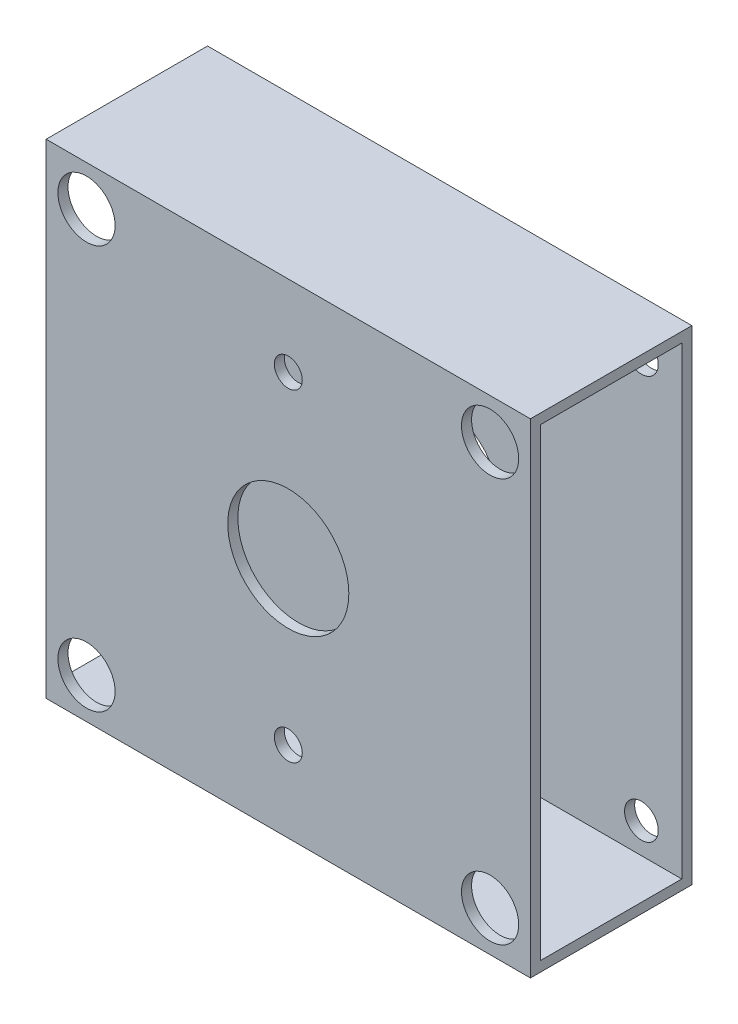
SolidWorks part; units mm, degrees
material "ALUMINUM 6061-T6"
ref_plane "Front Plane" through (0, 0, 0) normal (0, 0, 1) x (1, 0, 0)
ref_plane "Top Plane" through (0, 0, 0) normal (0, 1, 0) x (1, 0, 0)
ref_plane "Right Plane" through (0, 0, 0) normal (1, 0, 0) x (0, 0, -1)
sketch "Sketch1" plane through (0, 0, 0) normal (0, 0, 1) x (1, 0, 0)
  line L1 (-38.1, -38.1) -> (38.1, -38.1)
  line L2 (-38.1, -38.1) -> (-38.1, 38.1)
  line L3 (-38.1, 38.1) -> (38.1, 38.1)
  line L4 (38.1, -38.1) -> (38.1, 38.1)
  line L5 (-38.1, -38.1) -> (38.1, 38.1) construction
  line L6 (-38.1, 38.1) -> (38.1, -38.1) construction
  point P0 (0, 0)
  dimension "D1" = 76.2
  dimension "D2" = 76.2
extrude "Boss-Extrude1" add sketch "Sketch1" along normal mid plane 25.4
sketch "Sketch2" plane through (38.1, 0, 0) normal (1, 0, 0) x (0, 0, -1)
  line L8 (11.1125, -36.5125) -> (11.1125, 36.5125)
  line L9 (11.1125, 36.5125) -> (-11.1125, 36.5125)
  line L10 (-11.1125, 36.5125) -> (-11.1125, -36.5125)
  line L11 (-11.1125, -36.5125) -> (11.1125, -36.5125)
  line L12 (11.1125, -36.5125) -> (11.1125, 36.5125)
  line L13 (11.1125, 36.5125) -> (-11.1125, 36.5125)
  line L14 (-11.1125, 36.5125) -> (-11.1125, -36.5125)
  line L15 (-11.1125, -36.5125) -> (11.1125, -36.5125)
  dimension "D1" = 1.5875
extrude "Cut-Extrude1" cut sketch "Sketch2" against normal through all
sketch "Sketch4" plane through (0, 0, 12.7) normal (0, 0, 1) x (1, 0, 0)
  line L0 (-38.1, 38.1) -> (38.1, -38.1) construction
  line L1 (38.1, -38.1) -> (-38.1, -38.1) construction
  line L2 (-38.1, -38.1) -> (38.1, 38.1) construction
  line L3 (38.1, 38.1) -> (38.1, 0) construction
  line L4 (38.1, -38.1) -> (38.1, 38.1) construction
  line L5 (38.1, 0) -> (-38.1, 0) construction
  line L6 (-38.1, 38.1) -> (-38.1, -38.1) construction
  line L7 (-38.1, 0) -> (-38.1, 38.1) construction
  line L8 (-38.1, 38.1) -> (0, 38.1) construction
  line L9 (38.1, 38.1) -> (-38.1, 38.1) construction
  line L10 (0, 38.1) -> (0, -38.1) construction
  line L11 (0, -38.1) -> (38.1, -38.1) construction
  circle A0 centre (0, 0) radius 9.525
  circle A1 centre (0, 25.4) radius 2.2
  circle A2 centre (-31.75, 31.75) radius 2.369
  circle A3 centre (31.75, 31.75) radius 2.1142
  circle A4 centre (-31.75, -31.75) radius 2.3154
  circle A5 centre (31.75, -31.75) radius 1.7996
  circle A6 centre (0, -25.4) radius 2.2
  dimension "D1" = 19.05
  dimension "D4" = 12.7
  dimension "D8" = 4.4
  dimension "D9" = 4.4
  dimension "D10" = 4.7379
  dimension "D2" = 25.4
  dimension "D3" = 25.4
  dimension "D5" = 6.35
  dimension "D6" = 6.35
  dimension "D7" = 6.35
extrude "Cut-Extrude2" cut sketch "Sketch4" against normal through all
hole_wizard "CBORE for M5 Socket Head Cap Screw1" positions "Sketch7" profile "Sketch6" counterbore size "M5" standard "Lanco STD" end condition through all
sketch "Sketch7" plane through (0, 0, 12.7) normal (0, 0, 1) x (1, 0, 0)
  point P0 (-31.75, 31.75)
  point P3 (31.75, 31.75)
  point P6 (31.75, -31.75)
  point P9 (-31.75, -31.75)
sketch "Sketch6" plane through (-31.75, 31.75, 12.7) normal (1, 0, 0) x (0, -1, 0)
  line L0 (0, 0) -> (0, 25.4)
  line L1 (0, 25.4) -> (2.65, 25.4)
  line L3 (2.65, 25.4) -> (2.65, 5.4)
  line L4 (2.65, 5.4) -> (4.5, 5.4)
  line L5 (4.5, 5.4) -> (4.5, 0)
  line L7 (4.5, 0) -> (0, 0)
  line L11 (0, -6.35) -> (0, 107.95) construction
  dimension "Thru Hole Dia." = 5.3
  dimension "Thru Hole Depth" = 25.4
  dimension "C'Bore Dia." = 9
  dimension "C'Bore Depth" = 5.4
sketch "Sketch8" plane through (0, 0, -12.7) normal (0, 0, -1) x (-1, 0, 0)
  circle A0 centre (0, 25.4) radius 3.81
  circle A1 centre (0, -25.4) radius 3.81
  dimension "D1" = 7.62
  dimension "D2" = 7.62
extrude "Cut-Extrude3" cut sketch "Sketch8" against normal up to next
sketch "Sketch9" plane through (0, 0, 12.7) normal (0, 0, 1) x (1, 0, 0)
  circle A0 centre (0, 0) radius 31.7771
